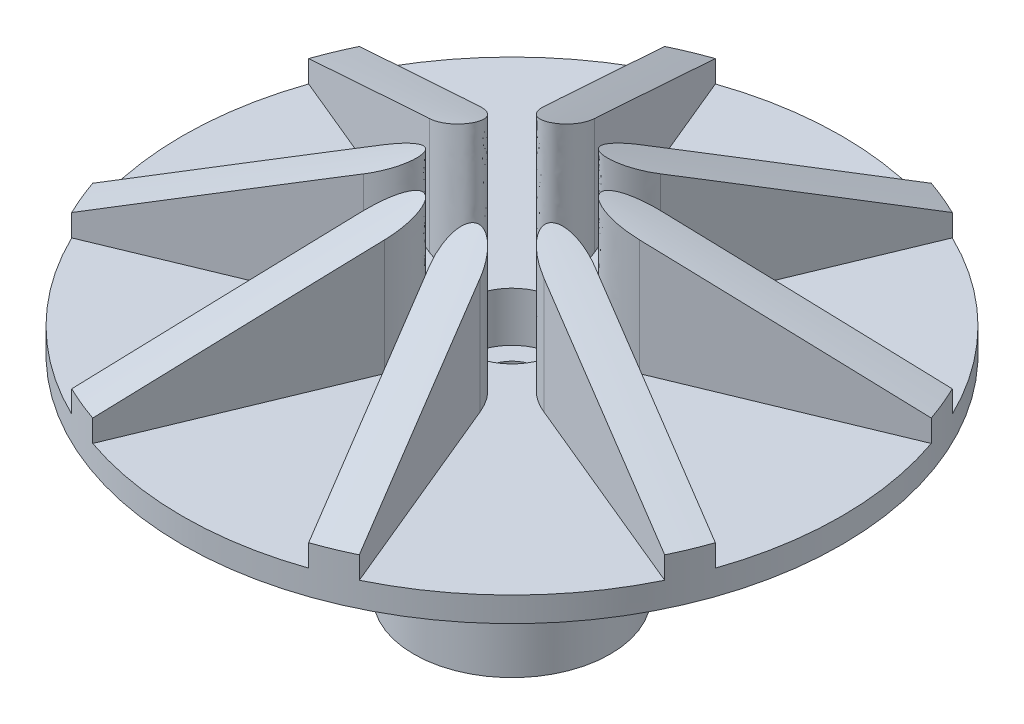
SolidWorks part; units mm, degrees
ref_plane "Front Plane" through (0, 0, 0) normal (0, 0, 1) x (1, 0, 0)
ref_plane "Top Plane" through (0, 0, 0) normal (0, 1, 0) x (1, 0, 0)
ref_plane "Right Plane" through (0, 0, 0) normal (1, 0, 0) x (0, 0, -1)
sketch "Sketch1" plane through (0, 0, 0) normal (0, 1, 0) x (1, 0, 0)
  circle A0 centre (0, 0) radius 26.6319
  dimension "D1" = 53.2638
extrude "impeller plate" add sketch "Sketch1" along normal blind 2
sketch "Sketch6" plane through (0, 0, 0) normal (0, -1, 0) x (-1, 0, 0)
  circle A0 centre (0, 0) radius 7.9375
  dimension "D1" = 15.875
extrude "boss" add sketch "Sketch6" along normal blind 17
sketch "Sketch7" plane through (0, -17, 0) normal (0, -1, 0) x (-1, 0, 0)
  circle A0 centre (0, 0) radius 2.1828
  dimension "D1" = 4.3656
extrude "bolt bore" cut sketch "Sketch7" against normal through all
sketch "Sketch8" plane through (0, -17, 0) normal (0, -1, 0) x (-1, 0, 0)
  circle A0 centre (0, 0) radius 4
  dimension "D1" = 8
extrude "shaft bore" cut sketch "Sketch8" against normal blind 12
sketch "Sketch9" plane through (0, 2, 0) normal (0, 1, 0) x (1, 0, 0)
  circle A0 centre (0, 0) radius 3.75
  dimension "D1" = 7.5
extrude "bolt head bore" cut sketch "Sketch9" against normal blind 4
sketch "Sketch11" plane through (0, -17, 0) normal (0, -1, 0) x (1, 0, 0)
  line L1 (-6, 1) -> (6, 1)
  line L2 (-6, 1) -> (-6, -1)
  line L3 (-6, -1) -> (6, -1)
  line L4 (6, 1) -> (6, -1)
  line L5 (-6, 1) -> (6, -1) construction
  line L6 (-6, -1) -> (6, 1) construction
  point P0 (0, 0)
  dimension "D1" = 12
  dimension "D2" = 2
extrude "dowel slot" cut sketch "Sketch11" against normal blind 3
sketch "Sketch12" plane through (0, 2, 0) normal (0, 1, 0) x (1, 0, 0)
  line L0 (0, 0) -> (26.6319, 0) construction
  line L1 (5.2287, 1.3897) -> (26.5956, 1.3897)
  line L2 (5.2287, -1.3897) -> (26.5956, -1.3897)
  circle A0 centre (0, 0) radius 26.6319 construction
  arc A3 (26.5956, -1.3897) -> (26.5956, 1.3897) centre (0, 0) ccw
  arc A4 (5.2287, -1.3897) -> (5.2287, 1.3897) centre (0, 0) ccw
  dimension "D3" = 10.8204
  dimension "D1" = 1.3897
  dimension "D2" = 1.3897
extrude "opening alingment cut" cut sketch "Sketch12" against normal blind 1
pattern_circular "opening alingment pattern" count 8 over 360 about axis through (0, 2, 0) along (0, 1, 0) of "opening alingment cut"
sketch "Sketch14" plane through (0, 2, 0) normal (0, 1, 0) x (1, 0, 0)
  line L0 (0, 0) -> (26.6319, 0) construction
  line L1 (26.5956, 1.3897) -> (5.2287, 1.3897) construction
  line L2 (7.2942, 4.7175) -> (8.4935, 1.822) construction
  line L3 (25.1617, 8.7262) -> (8.4935, 1.822) construction
  line L4 (7.8938, 3.2697) -> (4.9984, 2.0704) construction
  line L5 (0, 0) -> (24.6047, 10.1916) construction
  line L7 (7.2942, 4.7175) -> (23.9624, 11.6217)
  line L9 (8.4935, 1.822) -> (25.1617, 8.7262)
  arc A2 (26.5956, -1.3897) -> (26.5956, 1.3897) centre (0, 0) ccw construction
  arc A5 (26.5956, 1.3897) -> (19.7886, 17.8232) centre (0, 0) ccw construction
  circle A6 centre (0, 0) radius 5.4102 construction
  circle A7 centre (0, 0) radius 5.4102 construction
  arc A8 (25.1617, 8.7262) -> (23.9624, 11.6217) centre (0, 0) ccw
  ellipse E0 centre (7.8938, 3.2697) end of major axis (10.7893, 4.4691) minor radius 1.567 (7.2942, 4.7175) -> (8.4935, 1.822) ccw
  dimension "D1" = 22.5
extrude "one blade" add sketch "Sketch14" along normal blind 10.7467
sketch "Sketch15" plane through (0, 2, 0) normal (0, 1, 0) x (1, 0, 0)
  circle A0 centre (0, 0) radius 26.6319
  arc A1 (-19.7886, 17.8232) -> (-26.5956, 1.3897) centre (0, 0) ccw construction
  circle A2 centre (0, 0) radius 3.75
  circle A3 centre (0, 0) radius 3.75 construction
extrude "opening alignment fill" add sketch "Sketch15" against normal blind 2
pattern_circular "CirPattern2" count 8 over 360 about axis through (0, 2, 0) along (0, 1, 0) of "one blade"
sketch "Sketch16" plane through (0, 0, 0) normal (1, 0, 0) x (0, 0, -1)
  line L0 (0, 0) -> (0, 12.7467) construction
  line L2 (26.6319, 0) -> (26.6319, 3.778) construction
  line L3 (0, 12.7467) -> (5.4102, 12.7467) construction
  line L4 (5.4102, 12.7467) -> (26.6319, 3.778)
  line L5 (26.6319, 3.778) -> (26.6319, 12.7467)
  line L6 (26.6319, 12.7467) -> (5.4102, 12.7467)
  line L7 (-26.6319, 0) -> (26.6319, 0) construction
  dimension "D1" = 3.778
  dimension "D2" = 5.4102
  dimension "D3" = 26.6319
  dimension "D4" = 12.7467
revolve "angle cut" cut sketch "Sketch16" angle 360 about L0
equation "\"z\" = 8 \t\t\t'number of blades"
equation "\"de_length\" = 10mm\t\t'entrance eye consistent length"
equation "\"av\" = \"ae\"*\"av_ratio\"\t\t'area between just two blades"
equation "\"d2\" = 2.097in \t\t\t'outer diameter of the impeller"
equation "\"theta\" = 25\t\t\t'angle of blades from inner to outer "
equation "\"b2\" = .07in\t\t\t\t\t\t\t'tip height from disc surface at d2"
equation "\"b1\" = \"b2\" + (\"d2\"/2 - \"de\"/2)*sin(\"theta\") \t\t\t'tip height from disc surface at inlet eye"
equation "\"impeller base thickness\"= 2mm"
equation "\"impeller dowel diameter\" = 2mm"
equation "\"impeller bolt head diameter\" = \"m4 head bore diameter\""
equation "\"impeller bolt head depth\" = 4mm"
equation "\"impeller bolt stop depth\" = 3mm"
equation "\"impeller bolt bore\" = \"m4 clearance\""
equation "\"impeller shaft bore depth\" = 12mm"
equation "\"impeller shaft bore\" = 8mm"
equation "\"impeller boss depth\" = \"impeller shaft bore depth\"+\"impeller bolt stop depth\"+\"impeller bolt head depth\"-\"impeller base thickness\""
equation "\"impeller boss diameter\" = \"upper seal ID\""
equation "\"impeller dowel length\" = 2mm*2 + \"impeller shaft bore\""
equation "\"D1@Sketch1\"=\"d2\""
equation "\"D1@impeller plate\" = \"impeller base thickness\""
equation "\"D1@Sketch6\"=\"impeller boss diameter\""
equation "\"D1@boss\" = \"impeller boss depth\""
equation "\"D1@Sketch7\"=\"impeller bolt bore\""
equation "\"D1@Sketch8\"= \"impeller shaft bore\""
equation "\"D1@shaft bore\" = \"impeller shaft bore depth\""
equation "\"D1@Sketch9\"=\"impeller bolt head diameter\""
equation "\"D1@bolt head bore\" = \"impeller bolt head depth\""
equation "\"D1@Sketch11\"=\"impeller dowel length\""
equation "\"D2@Sketch11\"=\"impeller dowel diameter\""
equation "\"D1@dowel slot\" = \"impeller dowel diameter\" + 1mm"
equation "\"ae\" = 3.14*(\"de\"^2)/4\t\t'entrance eye area'"
equation "\"av_ratio\" = .325\t\t'ratio of av/ae at N_s of 470, range is .275 to .375, .325 ideal. High ratio means bigger area means smaller blades"
equation "\"s_open\" = \"av\"/\"b1\"\t\t'width of open area"
equation "\"de\" = 0.426in\t\t\t'entrance eye diameter"
equation "\"ce\" = 3.14*\"de\"\t\t'entrance eye circumference"
equation "\"D1@Sketch12\"=\"s_open\"/2"
equation "\"D3@Sketch12\"=\"de\""
equation "\"D1@opening alingment pattern\" = \"z\""
equation "\"D2@Sketch12\"=\"s_open\"/2"
equation "\"D1@one blade\" = \"b1\""
equation "\"D1@opening alignment fill\" = \"impeller base thickness\""
equation "\"D1@CirPattern2\"=\"z\""
equation "\"D1@Sketch16\"=\"impeller base thickness\"+\"b2\""
equation "\"D2@Sketch16\"=\"de\"/2"
equation "\"D3@Sketch16\"=\"d2\"/2"
equation "\"D1@Sketch14\"=360/\"z\"/2"
equation "\"D4@Sketch16\"=\"b1\"+\"impeller base thickness\""
equation "\"s\"=\"ce\" - \"z\"*\"s_open\""
equation "\"upper seal ID\"= 0.625in"
equation "\"m4 clearance\" = 0.171875in \t'this is 11/64 bit for 4.36mm"
equation "\"m4 tap\" = 0.125in\t\t'this is 1/8 bit for 3.17mm"
equation "\"m4 head bore diameter\" = 7.5mm"
equation "\"m4 head bore depth\" = 5mm\t'actual is ~4mm"
